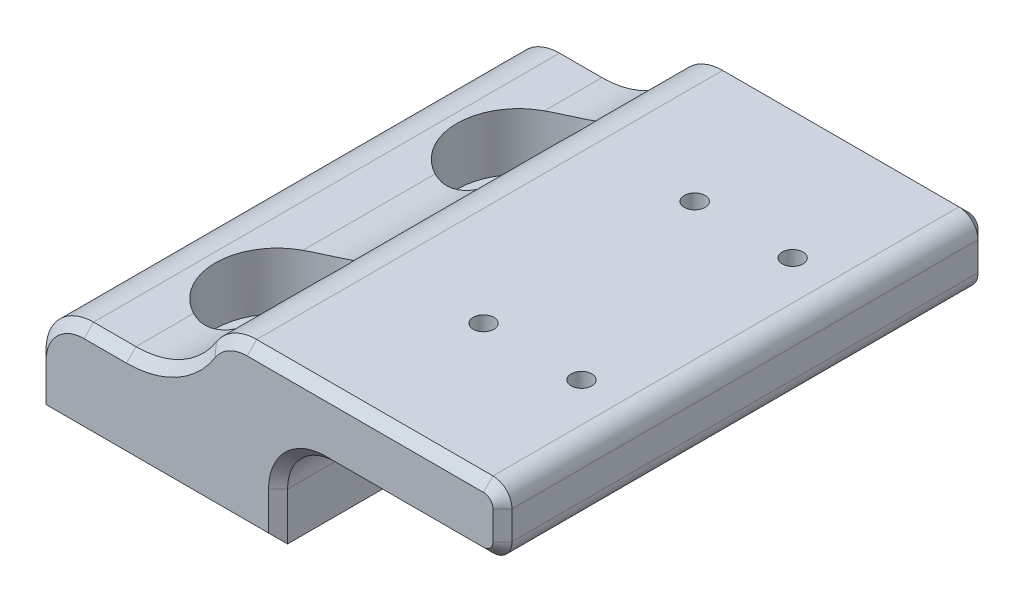
SolidWorks part; units mm, degrees
note: The reader was unsure of these and kept them because the rebuilt part matched: shared geometry of "Sketch3<4>".
ref_plane "Front Plane" through (0, 0, 0) normal (0, 0, 1) x (1, 0, 0)
ref_plane "Top Plane" through (0, 0, 0) normal (0, 1, 0) x (1, 0, 0)
ref_plane "Right Plane" through (0, 0, 0) normal (1, 0, 0) x (0, 0, -1)
sketch "Sketch1" plane through (0, 0, 0) normal (0, 0, 1) x (1, 0, 0)
  line L0 (-22.2, -8.5) -> (3.2, -8.5)
  line L5 (3.2, -8.5) -> (3.2, 1.5)
  line L6 (3.2, 1.5) -> (26.8, 1.5)
  line L7 (26.8, 1.5) -> (26.8, 8.5)
  line L8 (26.8, 8.5) -> (-3.2, 8.5)
  line L9 (-3.2, 8.5) -> (-3.2, 1.5)
  line L10 (-3.2, 1.5) -> (-22.2, 1.5)
  line L11 (-22.2, 1.5) -> (-22.2, -8.5)
  line L12 (0, 8.5) -> (0, -8.5) construction
  line L13 (-3.2, 0) -> (3.2, 0) construction
  point P13 (0, 0)
  point P22 (0, 0)
  dimension "D1" = 10
  dimension "D2" = 30
  dimension "D3" = 25.4
  dimension "D4" = 19
  dimension "D5" = 10
  dimension "D6" = 7
extrude "Boss-Extrude1" add sketch "Sketch1" along normal mid plane 51
sketch "Sketch3" plane through (0, 1.5, 0) normal (0, 1, 0) x (1, 0, 0)
  line L0 (-3.2, -25.5) -> (-3.2, 25.5) construction
  circle A0 centre (-9.7, -12.7) radius 6.5
  circle A1 centre (-9.7, -12.7) radius 2.921
  dimension "D1" = 13
  dimension "D2" = 5.842
  dimension "D3" = 12.7
extrude "Cut-Extrude1" cut sketch "Sketch3" against normal through all contours A1
extrude "Cut-Extrude2" cut sketch "Sketch3<4>" against normal blind 6
sketch "Sketch3<4>" plane through (0, 1.5, 0) normal (0, 1, 0) x (1, 0, 0) same geometry as "Sketch3"
mirror "Mirror1" about plane through (0, 0, 0) normal (0, 0, 1) of "Cut-Extrude2", "Cut-Extrude1"
sketch "Sketch9" plane through (0, 8.5, 0) normal (0, 1, 0) x (1, 0, 0)
  line L0 (10.4078, 11.1) -> (20.7078, -11.1) construction
  line L1 (26.8, -25.5) -> (26.8, 25.5) construction
  circle A0 centre (10.4078, 11.1) radius 1.0922
  circle A1 centre (20.7078, -11.1) radius 1.0922
  circle A2 centre (20.7078, 11.1) radius 1.0922
  circle A3 centre (10.4078, -11.1) radius 1.0922
  point P4 (15.5578, 0)
  point P11 (0, 0)
  point P12 (0, 0)
  point P13 (0, 0)
  point P15 (0, 0)
  point P16 (0, 0)
  dimension "D3" = 2.1844
  dimension "D1" = 22.2
  dimension "D2" = 10.3
  dimension "D4" = 5
extrude "Cut-Extrude3" cut sketch "Sketch9" against normal through all
fillet "Fillet1" radius 10 3 edges at (-3.2, 1.5, 19.1) (-3.2, 1.5, -19.1) (-3.2, 1.5, 0)
fillet "Fillet2" radius 5 3 edges at (-3.2, 8.5, -19.1) (3.2, 1.5, 0) (-22.2, 1.5, 0)
fillet "Fillet4" radius 2 2 edges at (26.8, 8.5, 0) (26.8, 1.5, 0)
chamfer "Chamfer1" distance 1 angle 45 26 edges at (26.8, 5, 25.5) (16.5, 1.5, 25.5) (4.6645, 0.0355, 25.5) (3.2, -6, 25.5) (-9.5, -8.5, 25.5) (-22.2, -6, 25.5) (-14.9697, 1.5, 25.5) (-7.9089, 2.744, 25.5) (-2.466, 7.878, 25.5) (12.3746, 8.5, 25.5) (-14.9697, 1.5, -25.5) (-22.2, -6, -25.5) (-9.5, -8.5, -25.5) (3.2, -6, -25.5) (4.6645, 0.0355, -25.5) (16.5, 1.5, -25.5) (26.8, 5, -25.5) (12.3746, 8.5, -25.5) (-2.466, 7.878, -25.5) (-7.9089, 2.744, -25.5) (26.2142, 2.0858, 25.5) (-20.7355, 0.0355, 25.5) (26.2142, 7.9142, 25.5) (-20.7355, 0.0355, -25.5) (26.2142, 2.0858, -25.5) (26.2142, 7.9142, -25.5)
